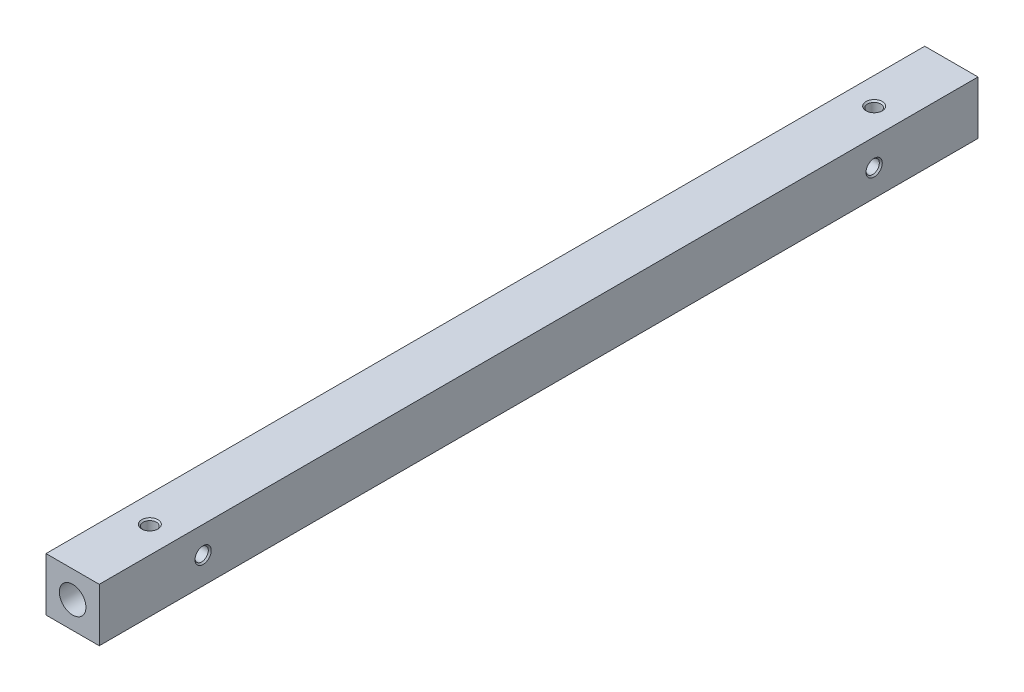
SolidWorks part; units mm, degrees
ref_plane "Plan de face" through (0, 0, 0) normal (0, 0, 1) x (1, 0, 0)
ref_plane "Plan de dessus" through (0, 0, 0) normal (0, 1, 0) x (1, 0, 0)
ref_plane "Plan de droite" through (0, 0, 0) normal (1, 0, 0) x (0, 0, -1)
sketch "Esquisse1" plane through (0, 0, 0) normal (0, 0, 1) x (1, 0, 0)
  line L0 (-5, 5) -> (5, -5) construction
  line L1 (-5, 5) -> (5, 5)
  line L2 (-5, 5) -> (-5, -5)
  line L3 (-5, -5) -> (5, -5)
  line L4 (5, 5) -> (5, -5)
  dimension "D1" = 10
extrude "Boss.-Extru.1" add sketch "Esquisse1" along normal mid plane 165
hole_wizard "Trou taraudé M3x0.51" positions "Esquisse3" profile "Esquisse2" tap size "M3x0.5" standard "Ansi Metric" end condition through all
sketch "Esquisse3" plane through (5, 0, 0) normal (1, 0, 0) x (0, 0, -1)
  point P0 (63, 0)
  point P3 (-63, 0)
sketch "Esquisse2" plane through (5, 0, -63) normal (0, 1, 0) x (0, 0, -1)
  line L0 (0, 0) -> (0, 10)
  line L1 (0, 10) -> (1.25, 10)
  line L2 (1.25, 10) -> (1.25, 0.275)
  line L3 (1.25, 0.275) -> (1.525, 0)
  line L5 (1.525, 0) -> (0, 0)
  line L6 (-1.25, 0.275) -> (-1.525, 0) construction
  line L11 (0, -6.35) -> (0, 107.95) construction
  dimension "Diamètre du trou pour taraudage jusqu'au prochain" = 2.5
  dimension "Profondeur du trou pour taraudage jusqu'au prochain" = 10
  dimension "Diamètre du fraisage entrant" = 3.05
  dimension "Angle du fraisage entrant" = 90
cosmetic thread "Filetage de perçage1" parameters "D2"=3
cosmetic thread "Filetage de perçage2" parameters "D2"=3
hole_wizard "Trou taraudé M3x0.52" positions "Esquisse5" profile "Esquisse4" tap size "M3x0.5" standard "Ansi Metric" end condition through all
sketch "Esquisse5" plane through (0, 5, 0) normal (0, 1, 0) x (1, 0, 0)
  line L0 (0, 0) -> (-36.1539, 0) construction
  line L2 (5, 82.5) -> (-5, 82.5) construction
  point P0 (0, 68)
  point P2 (0, -68)
  dimension "D1" = 68
  dimension "D2" = 14.5
sketch "Esquisse4" plane through (0, 5, -68) normal (1, 0, 0) x (0, 0, 1)
  line L0 (0, 0) -> (0, 10)
  line L1 (0, 10) -> (1.25, 10)
  line L2 (1.25, 10) -> (1.25, 0.275)
  line L3 (1.25, 0.275) -> (1.525, 0)
  line L5 (1.525, 0) -> (0, 0)
  line L6 (-1.25, 0.275) -> (-1.525, 0) construction
  line L11 (0, -6.35) -> (0, 107.95) construction
  dimension "Diamètre du trou pour taraudage jusqu'au prochain" = 2.5
  dimension "Profondeur du trou pour taraudage jusqu'au prochain" = 10
  dimension "Diamètre du fraisage entrant" = 3.05
  dimension "Angle du fraisage entrant" = 90
cosmetic thread "Filetage de perçage3" parameters "D2"=3
cosmetic thread "Filetage de perçage4" parameters "D2"=3
sketch "Esquisse6" plane through (0, 0, 82.5) normal (0, 0, 1) x (1, 0, 0)
  circle A0 centre (0, 0) radius 2.5
  dimension "D1" = 5
extrude "Enlèv. mat.-Extru.1" cut sketch "Esquisse6" against normal blind 6
sketch "Esquisse7" plane through (0, 0, -82.5) normal (0, 0, -1) x (-1, 0, 0)
  circle A0 centre (0, 0) radius 2.5
  dimension "D1" = 5
extrude "Enlèv. mat.-Extru.2" cut sketch "Esquisse7" against normal blind 6
